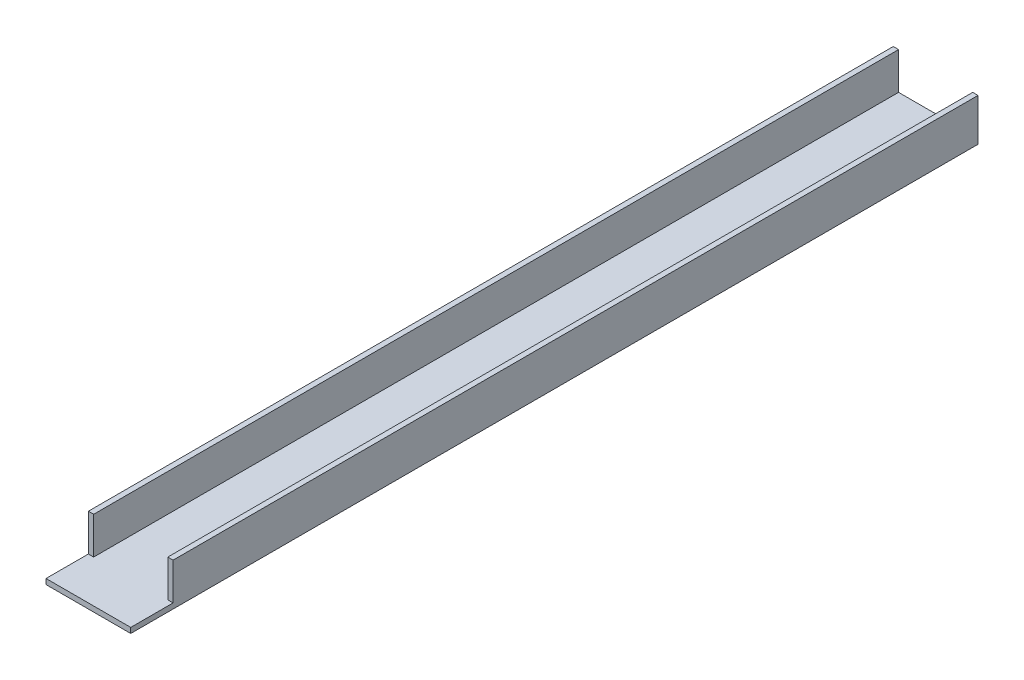
SolidWorks part; units mm, degrees
material "6063-T6"
ref_plane "Front" through (0, 0, 0) normal (0, 0, 1) x (1, 0, 0)
ref_plane "Top" through (0, 0, 0) normal (0, 1, 0) x (1, 0, 0)
ref_plane "Right" through (0, 0, 0) normal (1, 0, 0) x (0, 0, -1)
sketch "Sketch1" plane through (0, 0, 0) normal (0, 0, 1) x (1, 0, 0)
  line L0 (3.175, 3.175) -> (3.175, 25.4)
  line L1 (0, 0) -> (50.8, 0)
  line L2 (0, 0) -> (0, 25.4)
  line L4 (50.8, 0) -> (50.8, 25.4)
  line L5 (3.175, 3.175) -> (47.625, 3.175)
  line L6 (47.625, 3.175) -> (47.625, 25.4)
  line L7 (0, 25.4) -> (3.175, 25.4)
  line L8 (50.8, 25.4) -> (47.625, 25.4)
  dimension "D1" = 25.4
  dimension "D2" = 50.8
  dimension "D3" = 3.175
extrude "Boss-Extrude1" add sketch "Sketch1" along normal blind 508
sketch "Sketch2" plane through (0, 25.4, 0) normal (0, 1, 0) x (1, 0, 0)
  line L0 (0, -508) -> (0, 0) construction
  line L1 (50.8, -508) -> (0, -508)
  line L2 (50.8, -508) -> (50.8, -482.6)
  line L3 (50.8, -482.6) -> (0, -482.6)
  line L4 (0, -508) -> (0, -482.6)
  line L5 (50.8, -508) -> (0, -482.6) construction
  line L6 (50.8, -482.6) -> (0, -508) construction
  point P4 (25.4, -495.3)
  dimension "D1" = 25.4
extrude "Cut-Extrude1" cut sketch "Sketch2" against normal up to surface (22.225 mm away) up to face at (25.4, 3.175, 254)
